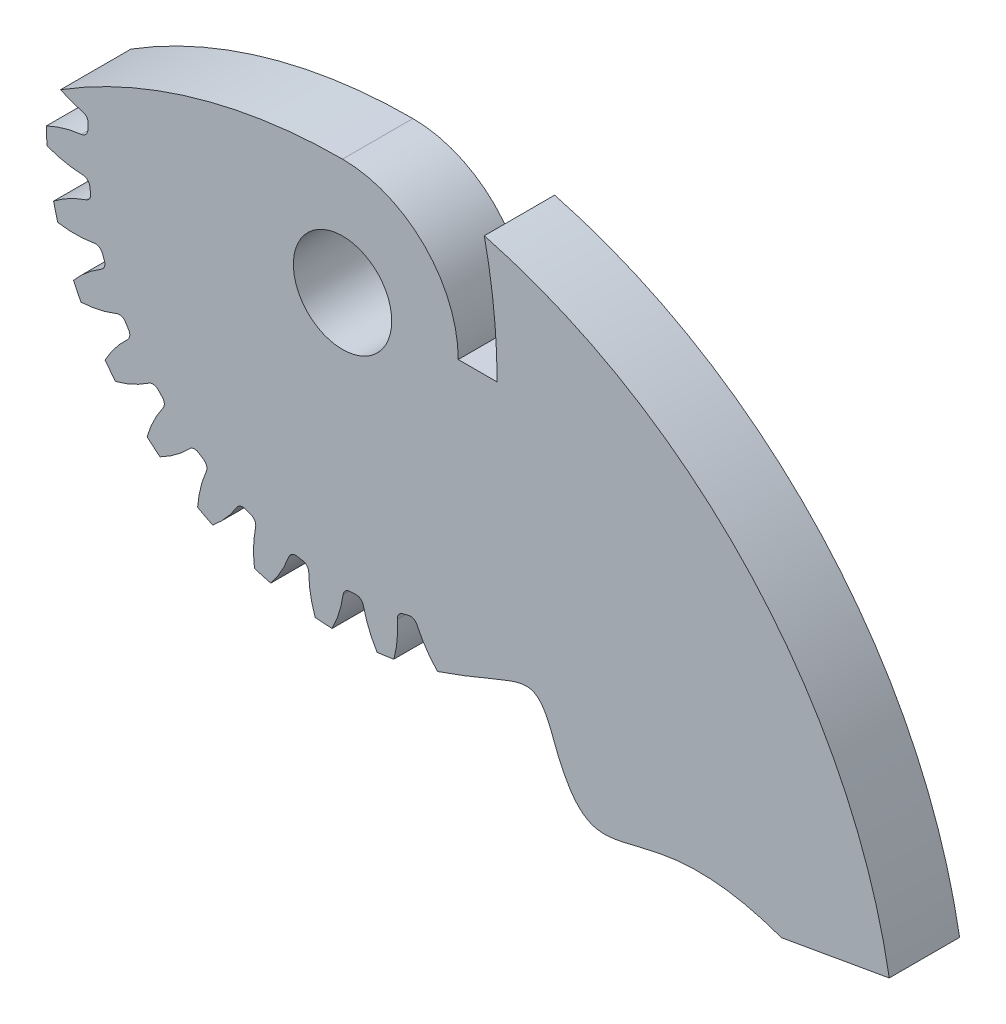
SolidWorks part; units mm, degrees
material "ABS"
ref_plane "Front" through (0, 0, 0) normal (0, 0, 1) x (1, 0, 0)
ref_plane "Top" through (0, 0, 0) normal (0, 1, 0) x (1, 0, 0)
ref_plane "Right" through (0, 0, 0) normal (1, 0, 0) x (0, 0, -1)
sketch "Sketch3" plane through (0, 0, 0) normal (0, 0, 1) x (1, 0, 0)
  circle A0 centre (0, 0) radius 40.64
  dimension "od" = 81.28
extrude "gearBody" add sketch "Sketch3" along normal blind 9.652
sketch "Sketch2" plane through (0, 0, 0) normal (0, 0, 1) x (1, 0, 0)
  line L0 (0, 0) -> (34.0786, 14.1158) construction
  line L1 (45.4751, -11.4855) -> (0, 0) construction
  line L2 (0, 0) -> (36.3143, 0) construction
  line L3 (38.0972, -0.458) -> (37.8451, -4.4001) construction
  line L5 (37.9712, -2.4291) -> (0, 0) construction
  line L7 (0, 0) -> (36.8864, 0) construction
  arc A0 (36.879, -0.7403) -> (36.6727, -3.9649) centre (0, 0) ccw construction
  arc A1 (40.637, 0.4947) -> (40.2427, -5.6687) centre (0, 0) ccw construction
  arc A2 (38.0972, -0.458) -> (37.8451, -4.4001) centre (0, 0) ccw construction
  arc A3 (34.9015, -2.6404) -> (34.9534, -1.8283) centre (0, 0) ccw
  arc A4 (45.4751, -11.4855) -> (35.6466, -3.6712) centre (32.0022, -18.3431) ccw
  arc A5 (45.4751, -11.4855) -> (46.5679, 5.5974) centre (0, 0) ccw
  arc A6 (46.5679, 5.5974) -> (35.8238, -0.9008) centre (34.0786, 14.1158) cw
  arc A7 (34.9534, -1.8283) -> (35.8238, -0.9008) centre (35.9376, -1.8798) cw
  arc A8 (35.6466, -3.6712) -> (34.9015, -2.6404) centre (35.8842, -2.7147) cw
  point P6 (46.5679, 5.5974)
  point P22 (45.4751, -11.4855)
  dimension "baseDia" = 73.7729
  dimension "od" = 81.28
  dimension "pd" = 76.2
  dimension "rd" = 70.0024
  dimension "rFillet" = 0.9855
  dimension "pointX" = 46.5679
  dimension "pointY" = 5.5974
  dimension "CTT" = 3.9421
  dimension "flankCenterAngle" = 22.5
extrude "toothCut" cut sketch "Sketch2" along normal through all
pattern_circular "CirPattern1" count 30 over 360 about axis through (0, 0, 9.652) along (0, 0, -1) of "toothCut"
sketch "hub1Dia" plane through (0, 0, 0) normal (0, 0, -1) x (-1, 0, 0)
  circle A0 centre (0, 0) radius 12.7
  dimension "hub1Dia" = 25.4
sketch "hub2Dia" plane through (0, 0, 9.652) normal (0, 0, 1) x (1, 0, 0)
  circle A0 centre (0, 0) radius 12.7
  dimension "hub2dia" = 25.4
sketch "boreDia" plane through (0, 0, 0) normal (0, 0, 1) x (1, 0, 0)
  circle A0 centre (0, 0) radius 6.7469
  dimension "boreDia" = 13.4937
extrude "bore" cut sketch "boreDia" against normal mid plane 25400
sketch "Sketch4" plane through (0, 0, 9.652) normal (0, 0, 1) x (1, 0, 0)
  circle A0 centre (0, -57.15) radius 76.1746
  arc A2 (-41.7195, 6.5842) -> (41.7195, 6.5842) centre (0, 0) cw
  dimension "D1" = 152.3492
  dimension "D2" = 57.15
extrude "Cut-Extrude1" cut sketch "Sketch4" against normal through all contours A0 region at (0, 26.0638, 9.652)
sketch "Sketch5" plane through (0, 0, 9.652) normal (0, 0, 1) x (1, 0, 0)
  line L0 (0, 19.0246) -> (21.5163, 3.7176)
  line L1 (21.5163, 3.7176) -> (8.9608, -26.928)
  line L2 (8.9608, -26.928) -> (13.028, -38.4952)
  line L3 (0, 0) -> (0, -57.15) construction
  line L4 (0, -57.15) -> (-54.1615, -3.586) construction
  line L5 (0, -57.15) -> (65.9691, -95.2373) construction
  line L9 (0, -57.15) -> (75.0173, -43.9224) construction
  line L12 (60.232, -46.5295) -> (75.0173, -43.9224)
  line L13 (0, -57.15) -> (29.696, -40.005) construction
  line L14 (29.696, -40.005) -> (26.521, -34.5057) construction
  circle A1 centre (0, -57.15) radius 76.1746 construction
  arc A5 (0, 19.0246) -> (75.0173, -43.9224) centre (0, -57.15) cw
  circle A6 centre (0, -57.15) radius 21.59 construction
  circle A12 centre (49.4934, -85.725) radius 40.64 construction
  spline S0 degree 3 poles (13.028, -38.4952) (20.557, -35.948) (26.6517, -31.726) (34.6651, -56.7545) (39.5345, -39.0169) (60.232, -46.5295) knots 0 0 0 0 0.118515 0.218515 1 1 1 1
  point P28 (21.569, -56.1981)
  dimension "D1" = 43.18
  dimension "D3" = 81.28
  dimension "D6" = 152.3492
  dimension "D2" = 120
  dimension "D4" = 57.15
  dimension "D8" = 57.15
  dimension "D7" = 60
  dimension "D9" = 34.29
  dimension "D10" = 6.35
  dimension "D5" = 80
extrude "Boss-Extrude1" add sketch "Sketch5" against normal up to surface (9.652 mm away) up to face at (6.7469, 0, 0)
sketch "Sketch6" plane through (0, 0, 9.652) normal (0, 0, 1) x (1, 0, 0)
  line L1 (-41.2993, 3.0747) -> (-42.3397, 6.1739)
  line L2 (15.875, 0) -> (21.209, 0)
  circle A0 centre (0, -57.15) radius 76.1746 construction
  arc A1 (75.0173, -43.9224) -> (-34.0662, 10.9827) centre (0, -57.15) ccw construction
  circle A2 centre (0, 0) radius 15.875 construction
  arc A3 (0, 15.875) -> (15.875, 0) centre (0, 0) cw
  arc A4 (19.4523, 16.499) -> (-42.3397, 6.1739) centre (0, -57.15) ccw
  arc A5 (0, 15.875) -> (-41.2993, 3.0747) centre (0, -57.15) ccw
  circle A6 centre (0, 0) radius 21.209 construction
  circle A8 centre (-57.15, 0) radius 78.359 construction
  arc A9 (21.209, 0) -> (19.4523, 16.499) centre (-57.15, 0) ccw
  dimension "D4" = 57.15
  dimension "D1" = 31.75
  dimension "D2" = 42.418
  dimension "D3" = 156.718
extrude "Cut-Extrude2" cut sketch "Sketch6" against normal through all
equation "\"Bodytube_OD\" = 6.17in"
equation "\"Bodytube_ID\" = 5.998in"
equation "\"Fwd_Tube_Length\" = 40in"
equation "\"Mid_Tube_Length\" = 1in"
equation "\"Aft_Section_Length\"= 39in"
equation "\"Mid_Coupler_Length\"= 13in"
equation "\"Aft_Lower_Length\"= 22in"
equation "\"AB_Coupler_OD_Length\"= 1in"
equation "\"AB_Coupling_Section_Length\"= 0.375in"
equation "\"AB_Coupler_Length\"= \"AB_Coupler_OD_Length\" + \"AB_Coupling_Section_Length\" * 2"
equation "\"Cutout_Angle\" = 80"
equation "\"AB_Paddle_Height\" = 0.375in"
equation "\"AB_Coupler_Num_Screws\"= 6"
equation "\"Num_Cutouts\" = 3"
equation "\"AB_Coupler_OD\"= 6.17in"
equation "\"AB_Coupler_ID\"= 5.75in"
equation "\"AB_Coupler_Surface_Diameter\"= 5.998in"
equation "\"AB_Coupling_Screw_Diameter\"= 0.1065in"
equation "\"AB_Central_Bushing_Length\" = .75in"
equation "\"Lead_Screw_Dist\" = 2.25in"
equation "\"Lead_Screw_Diam\" = 11mm"
equation "\"Lead_Screw_Length\" = (\"Mid_Coupler_Length\" + 2*0.375in + 2*0.5in)"
equation "\"Paddle_Pin_Offset\" = .25in"
equation "\"Paddle_Pin_Radius\" = 2.25in"
equation "\"Fwd_BKHD_From_Top\" = 18in"
equation "\"D1@Sketch4\"=\"Bodytube_ID\""
equation "\"D2@Sketch4\"=\"Paddle_Pin_Radius\""
equation "\"D3@Sketch5\"=\"Paddle_Gear_OD\""
equation "\"D4@Sketch5\"=\"Paddle_Pin_Radius\""
equation "\"Motor_OD\" = 4in"
equation "\"Aft_Upper_Length\"= \"Aft_Section_Length\" - \"Aft_Lower_Length\" - \"AB_Coupler_OD_Length\""
equation "\"Paddle_Gear_OD\" = 3.2in"
equation "\"D5@Sketch5\"=\"Cutout_Angle\""
equation "\"D6@Sketch5\"=\"Bodytube_ID\""
equation "\"D1@Sketch6\"=\"AB_Coupler_ID\"-2*\"Paddle_Pin_Radius\""
equation "\"D2@Sketch6\"=\"Bodytube_OD\"-2*\"Paddle_Pin_Radius\""
equation "\"D3@Sketch6\"=\"Bodytube_OD\""
equation "\"D4@Sketch6\"=\"Paddle_Pin_Radius\""
equation "\"D8@Sketch5\"=\"Paddle_Pin_Radius\""
equation "\"Drive_Gear_OD\" = 1.7in"
equation "\"Fin_Thickness\"= .118in"
equation "\"Guiderail_Cutout_Diameter\"= 1.5in"
equation "\"DB9_Hole_Dist\" = 25mm"
equation "\"D1@Sketch5\"=\"Drive_Gear_OD\""
